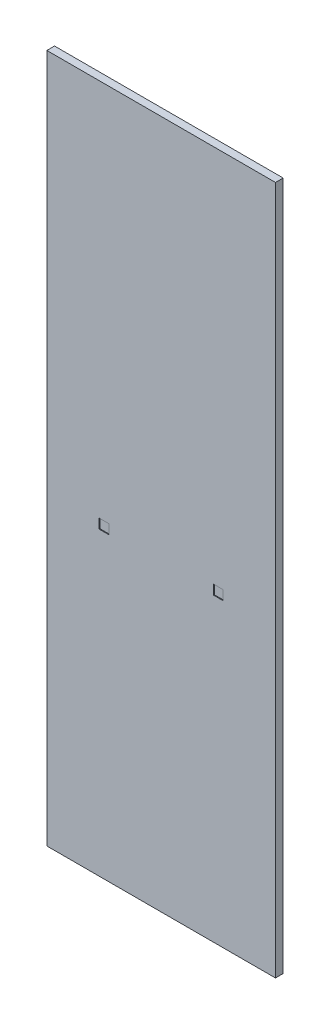
SolidWorks part; units mm, degrees
ref_plane "Front Plane" through (0, 0, 0) normal (0, 0, 1) x (1, 0, 0)
ref_plane "Top Plane" through (0, 0, 0) normal (0, 1, 0) x (1, 0, 0)
ref_plane "Right Plane" through (0, 0, 0) normal (1, 0, 0) x (0, 0, -1)
sketch "Sketch1" plane through (0, 0, 0) normal (0, 0, 1) x (1, 0, 0)
  line L1 (298, -898) -> (-298, -898)
  line L2 (298, -898) -> (298, 898)
  line L3 (298, 898) -> (-298, 898)
  line L4 (-298, -898) -> (-298, 898)
  line L5 (298, -898) -> (-298, 898) construction
  line L6 (298, 898) -> (-298, -898) construction
  point P0 (0, 0)
  dimension "D1" = 596
  dimension "D2" = 1796
extrude "Boss-Extrude1" add sketch "Sketch1" along normal blind 20
sketch "Sketch2" plane through (0, 0, 20) normal (0, 0, 1) x (1, 0, 0)
  line L0 (298, -102) -> (-298, -102) construction
  line L1 (298, -898) -> (298, 898) construction
  line L2 (-298, 898) -> (-298, -898) construction
  line L3 (298, 898) -> (-298, 898) construction
  line L4 (-149, 898) -> (-149, -898) construction
  line L5 (-298, -898) -> (298, -898) construction
  line L6 (149, 898) -> (149, -898) construction
  line L8 (-136.5, -114.5) -> (-161.5, -114.5)
  line L9 (-136.5, -114.5) -> (-136.5, -89.5)
  line L10 (-136.5, -89.5) -> (-161.5, -89.5)
  line L11 (-161.5, -114.5) -> (-161.5, -89.5)
  line L12 (-136.5, -114.5) -> (-161.5, -89.5) construction
  line L13 (-136.5, -89.5) -> (-161.5, -114.5) construction
  line L14 (161.5, -114.5) -> (136.5, -114.5)
  line L15 (161.5, -114.5) -> (161.5, -89.5)
  line L16 (161.5, -89.5) -> (136.5, -89.5)
  line L17 (136.5, -114.5) -> (136.5, -89.5)
  line L18 (161.5, -114.5) -> (136.5, -89.5) construction
  line L19 (161.5, -89.5) -> (136.5, -114.5) construction
  point P15 (-149, -102)
  point P20 (149, -102)
  dimension "D4" = 25
  dimension "D5" = 25
  dimension "D1" = 1000
  dimension "D2" = 149
  dimension "D3" = 149
  dimension "D6" = 25
  dimension "D7" = 25
extrude "Cut-Extrude1" cut sketch "Sketch2" against normal blind 2
sketch "Sketch3" plane through (0, 0, 20) normal (0, 0, 1) x (1, 0, 0)
  line L0 (0, 1012.9749) -> (0, -1086.4881) construction
  line L1 (-161.5, -102) -> (223.2509, -102) construction
  line L2 (-161.5, -89.5) -> (-161.5, -114.5) construction
  line L3 (-136.5, -114.5) -> (-136.5, -89.5) construction
  line L4 (136.5, -89.5) -> (136.5, -114.5) construction
  line L5 (-298, 898) -> (-298, -898) construction
  line L6 (298, -898) -> (298, 898) construction
  dimension "D1" = 298
  dimension "D2" = 298
  dimension "D3" = 136.5
  dimension "D4" = 136.5
